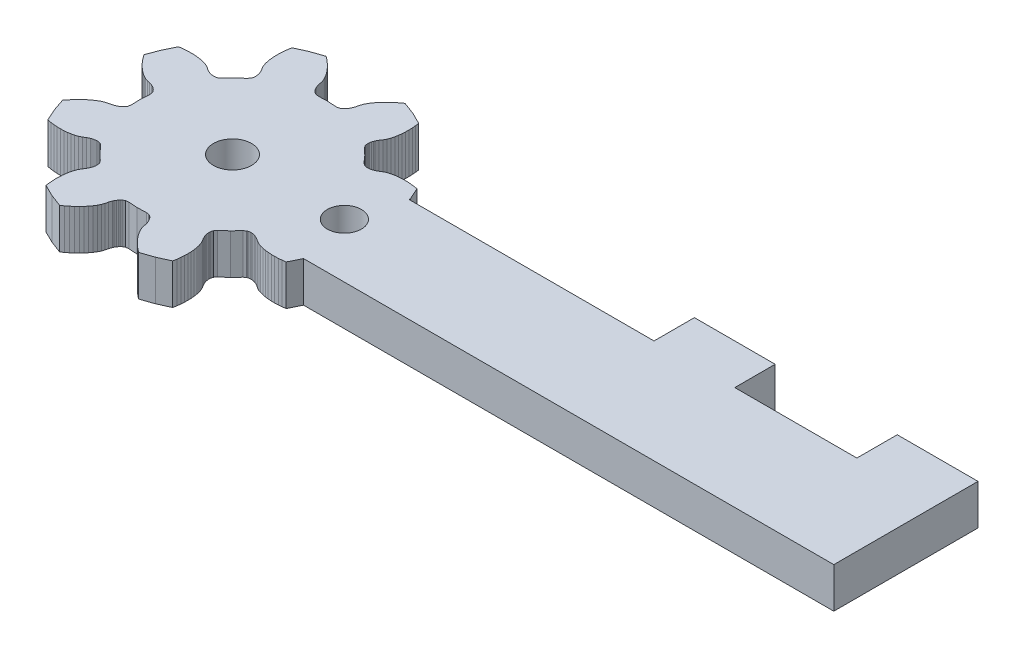
SolidWorks part; units mm, degrees
ref_plane "Front Plane" through (0, 0, 0) normal (0, 0, 1) x (1, 0, 0)
ref_plane "Top Plane" through (0, 0, 0) normal (0, 1, 0) x (1, 0, 0)
ref_plane "Right Plane" through (0, 0, 0) normal (1, 0, 0) x (0, 0, -1)
sketch "Sketch1" plane through (0, 0, 0) normal (0, 1, 0) x (1, 0, 0)
  line L0 (118.5341, 166.0961) -> (137.7907, 166.0961)
  line L1 (160.0907, 166.0961) -> (160.0907, 157.9324)
  line L2 (160.0907, 157.9324) -> (118.4045, 157.9258)
  line L3 (160.0907, 166.0961) -> (160.0907, 169.2711)
  line L4 (160.0907, 169.2711) -> (153.7407, 169.2711)
  line L5 (153.7407, 169.2711) -> (153.7407, 166.0961)
  line L7 (144.1407, 166.0961) -> (144.1407, 169.2711)
  line L8 (144.1407, 169.2711) -> (137.7907, 169.2711)
  line L9 (137.7907, 169.2711) -> (137.7907, 166.0961)
  line L10 (144.1407, 166.0961) -> (153.7407, 166.0961)
  line L1608 (118.5341, 166.0961) -> (118.5341, 166.193)
  line L1609 (118.5341, 166.193) -> (118.1081, 167.1345)
  line L1610 (118.1081, 167.1345) -> (117.8266, 167.1811)
  line L1611 (117.8266, 167.1811) -> (117.5494, 167.2141)
  line L1612 (117.5494, 167.2141) -> (117.277, 167.2336)
  line L1613 (117.277, 167.2336) -> (117.0101, 167.2392)
  line L1614 (117.0101, 167.2392) -> (116.7493, 167.2309)
  line L1615 (116.7493, 167.2309) -> (116.4956, 167.2082)
  line L1616 (116.4956, 167.2082) -> (116.2497, 167.1704)
  line L1617 (116.2497, 167.1704) -> (116.0133, 167.1164)
  line L1618 (116.0133, 167.1164) -> (115.7883, 167.0435)
  line L1619 (115.7883, 167.0435) -> (115.5824, 166.9415)
  line L1620 (115.5824, 166.9415) -> (115.3904, 166.8184)
  line L1621 (115.3904, 166.8184) -> (115.1836, 166.7174)
  line L1622 (115.1836, 166.7174) -> (115.0732, 166.6772)
  line L1623 (115.0732, 166.6772) -> (114.9567, 166.6456)
  line L1624 (114.9567, 166.6456) -> (114.8323, 166.6253)
  line L1625 (114.8323, 166.6253) -> (114.766, 166.6206)
  line L1626 (114.766, 166.6206) -> (114.696, 166.6208)
  line L1627 (114.696, 166.6208) -> (114.6211, 166.6276)
  line L1628 (114.6211, 166.6276) -> (114.5385, 166.6443)
  line L1629 (114.5385, 166.6443) -> (114.4416, 166.6792)
  line L1630 (114.4416, 166.6792) -> (114.2616, 166.8186)
  line L1631 (114.2616, 166.8186) -> (113.7953, 167.3484)
  line L1632 (113.7953, 167.3484) -> (113.2804, 167.8311)
  line L1633 (113.2804, 167.8311) -> (113.1468, 168.0154)
  line L1634 (113.1468, 168.0154) -> (113.1149, 168.1133)
  line L1635 (113.1149, 168.1133) -> (113.1008, 168.1964)
  line L1636 (113.1008, 168.1964) -> (113.0963, 168.2716)
  line L1637 (113.0963, 168.2716) -> (113.0983, 168.3415)
  line L1638 (113.0983, 168.3415) -> (113.1051, 168.4076)
  line L1639 (113.1051, 168.4076) -> (113.1293, 168.5313)
  line L1640 (113.1293, 168.5313) -> (113.1645, 168.6468)
  line L1641 (113.1645, 168.6468) -> (113.2082, 168.7559)
  line L1642 (113.2082, 168.7559) -> (113.3157, 168.9594)
  line L1643 (113.3157, 168.9594) -> (113.4447, 169.1474)
  line L1644 (113.4447, 169.1474) -> (113.5532, 169.35)
  line L1645 (113.5532, 169.35) -> (113.633, 169.5726)
  line L1646 (113.633, 169.5726) -> (113.6945, 169.8072)
  line L1647 (113.6945, 169.8072) -> (113.74, 170.0517)
  line L1648 (113.74, 170.0517) -> (113.7706, 170.3047)
  line L1649 (113.7706, 170.3047) -> (113.7871, 170.565)
  line L1650 (113.7871, 170.565) -> (113.7899, 170.832)
  line L1651 (113.7899, 170.832) -> (113.779, 171.1049)
  line L1652 (113.779, 171.1049) -> (113.7547, 171.383)
  line L1653 (113.7547, 171.383) -> (113.717, 171.6658)
  line L1654 (113.717, 171.6658) -> (112.7893, 172.1212)
  line L1655 (112.7893, 172.1212) -> (111.8223, 172.4857)
  line L1656 (111.8223, 172.4857) -> (111.5903, 172.3196)
  line L1657 (111.5903, 172.3196) -> (111.371, 172.1469)
  line L1658 (111.371, 172.1469) -> (111.1646, 171.9681)
  line L1659 (111.1646, 171.9681) -> (110.9718, 171.7833)
  line L1660 (110.9718, 171.7833) -> (110.7934, 171.593)
  line L1661 (110.7934, 171.593) -> (110.63, 171.3975)
  line L1662 (110.63, 171.3975) -> (110.4829, 171.197)
  line L1663 (110.4829, 171.197) -> (110.3539, 170.9916)
  line L1664 (110.3539, 170.9916) -> (110.2464, 170.781)
  line L1665 (110.2464, 170.781) -> (110.1728, 170.5633)
  line L1666 (110.1728, 170.5633) -> (110.1241, 170.3405)
  line L1667 (110.1241, 170.3405) -> (110.0493, 170.1228)
  line L1668 (110.0493, 170.1228) -> (109.9997, 170.0163)
  line L1669 (109.9997, 170.0163) -> (109.9397, 169.9116)
  line L1670 (109.9397, 169.9116) -> (109.8661, 169.8092)
  line L1671 (109.8661, 169.8092) -> (109.8225, 169.759)
  line L1672 (109.8225, 169.759) -> (109.7729, 169.7097)
  line L1673 (109.7729, 169.7097) -> (109.715, 169.6615)
  line L1674 (109.715, 169.6615) -> (109.6448, 169.615)
  line L1675 (109.6448, 169.615) -> (109.5516, 169.5712)
  line L1676 (109.5516, 169.5712) -> (109.3258, 169.5424)
  line L1677 (109.3258, 169.5424) -> (108.6215, 169.5873)
  line L1678 (108.6215, 169.5873) -> (107.9161, 169.5646)
  line L1679 (107.9161, 169.5646) -> (107.6912, 169.6004)
  line L1680 (107.6912, 169.6004) -> (107.5995, 169.6471)
  line L1681 (107.5995, 169.6471) -> (107.5307, 169.6959)
  line L1682 (107.5307, 169.6959) -> (107.4745, 169.7459)
  line L1683 (107.4745, 169.7459) -> (107.4264, 169.7967)
  line L1684 (107.4264, 169.7967) -> (107.3844, 169.8482)
  line L1685 (107.3844, 169.8482) -> (107.3141, 169.9529)
  line L1686 (107.3141, 169.9529) -> (107.2574, 170.0594)
  line L1687 (107.2574, 170.0594) -> (107.2111, 170.1674)
  line L1688 (107.2111, 170.1674) -> (107.1432, 170.3873)
  line L1689 (107.1432, 170.3873) -> (107.1015, 170.6115)
  line L1690 (107.1015, 170.6115) -> (107.0349, 170.8315)
  line L1691 (107.0349, 170.8315) -> (106.934, 171.0453)
  line L1692 (106.934, 171.0453) -> (106.8116, 171.2547)
  line L1693 (106.8116, 171.2547) -> (106.6708, 171.4597)
  line L1694 (106.6708, 171.4597) -> (106.5136, 171.6603)
  line L1695 (106.5136, 171.6603) -> (106.3412, 171.856)
  line L1696 (106.3412, 171.856) -> (106.1543, 172.0467)
  line L1697 (106.1543, 172.0467) -> (105.9537, 172.232)
  line L1698 (105.9537, 172.232) -> (105.7399, 172.4115)
  line L1699 (105.7399, 172.4115) -> (105.5133, 172.5848)
  line L1700 (105.5133, 172.5848) -> (104.5353, 172.2508)
  line L1701 (104.5353, 172.2508) -> (103.5937, 171.8248)
  line L1702 (103.5937, 171.8248) -> (103.5472, 171.5433)
  line L1703 (103.5472, 171.5433) -> (103.5141, 171.2661)
  line L1704 (103.5141, 171.2661) -> (103.4947, 170.9937)
  line L1705 (103.4947, 170.9937) -> (103.489, 170.7268)
  line L1706 (103.489, 170.7268) -> (103.4974, 170.4661)
  line L1707 (103.4974, 170.4661) -> (103.52, 170.2122)
  line L1708 (103.52, 170.2122) -> (103.5578, 169.9665)
  line L1709 (103.5578, 169.9665) -> (103.6119, 169.73)
  line L1710 (103.6119, 169.73) -> (103.6847, 169.5051)
  line L1711 (103.6847, 169.5051) -> (103.7867, 169.2991)
  line L1712 (103.7867, 169.2991) -> (103.9099, 169.1071)
  line L1713 (103.9099, 169.1071) -> (104.0108, 168.9003)
  line L1714 (104.0108, 168.9003) -> (104.0511, 168.7899)
  line L1715 (104.0511, 168.7899) -> (104.0826, 168.6735)
  line L1716 (104.0826, 168.6735) -> (104.103, 168.549)
  line L1717 (104.103, 168.549) -> (104.1077, 168.4827)
  line L1718 (104.1077, 168.4827) -> (104.1075, 168.4127)
  line L1719 (104.1075, 168.4127) -> (104.1006, 168.3378)
  line L1720 (104.1006, 168.3378) -> (104.0839, 168.2552)
  line L1721 (104.0839, 168.2552) -> (104.049, 168.1583)
  line L1722 (104.049, 168.1583) -> (103.9096, 167.9783)
  line L1723 (103.9096, 167.9783) -> (103.3799, 167.512)
  line L1724 (103.3799, 167.512) -> (102.8972, 166.9971)
  line L1725 (102.8972, 166.9971) -> (102.7129, 166.8635)
  line L1726 (102.7129, 166.8635) -> (102.6149, 166.8316)
  line L1727 (102.6149, 166.8316) -> (102.5318, 166.8175)
  line L1728 (102.5318, 166.8175) -> (102.4567, 166.8131)
  line L1729 (102.4567, 166.8131) -> (102.3868, 166.815)
  line L1730 (102.3868, 166.815) -> (102.3207, 166.8218)
  line L1731 (102.3207, 166.8218) -> (102.1969, 166.8461)
  line L1732 (102.1969, 166.8461) -> (102.0815, 166.8813)
  line L1733 (102.0815, 166.8813) -> (101.9724, 166.9249)
  line L1734 (101.9724, 166.9249) -> (101.7689, 167.0324)
  line L1735 (101.7689, 167.0324) -> (101.5809, 167.1615)
  line L1736 (101.5809, 167.1615) -> (101.3782, 167.2699)
  line L1737 (101.3782, 167.2699) -> (101.1557, 167.3498)
  line L1738 (101.1557, 167.3498) -> (100.921, 167.4112)
  line L1739 (100.921, 167.4112) -> (100.6765, 167.4567)
  line L1740 (100.6765, 167.4567) -> (100.4236, 167.4874)
  line L1741 (100.4236, 167.4874) -> (100.1632, 167.5039)
  line L1742 (100.1632, 167.5039) -> (99.8963, 167.5066)
  line L1743 (99.8963, 167.5066) -> (99.6234, 167.4957)
  line L1744 (99.6234, 167.4957) -> (99.3453, 167.4714)
  line L1745 (99.3453, 167.4714) -> (99.0625, 167.4337)
  line L1746 (99.0625, 167.4337) -> (98.6071, 166.506)
  line L1747 (98.6071, 166.506) -> (98.2426, 165.539)
  line L1748 (98.2426, 165.539) -> (98.4087, 165.3071)
  line L1749 (98.4087, 165.3071) -> (98.5813, 165.0877)
  line L1750 (98.5813, 165.0877) -> (98.7602, 164.8813)
  line L1751 (98.7602, 164.8813) -> (98.9449, 164.6886)
  line L1752 (98.9449, 164.6886) -> (99.1352, 164.5101)
  line L1753 (99.1352, 164.5101) -> (99.3307, 164.3467)
  line L1754 (99.3307, 164.3467) -> (99.5312, 164.1996)
  line L1755 (99.5312, 164.1996) -> (99.7367, 164.0706)
  line L1756 (99.7367, 164.0706) -> (99.9472, 163.9631)
  line L1757 (99.9472, 163.9631) -> (100.165, 163.8895)
  line L1758 (100.165, 163.8895) -> (100.3878, 163.8409)
  line L1759 (100.3878, 163.8409) -> (100.6054, 163.7661)
  line L1760 (100.6054, 163.7661) -> (100.7119, 163.7165)
  line L1761 (100.7119, 163.7165) -> (100.8166, 163.6564)
  line L1762 (100.8166, 163.6564) -> (100.919, 163.5828)
  line L1763 (100.919, 163.5828) -> (100.9692, 163.5392)
  line L1764 (100.9692, 163.5392) -> (101.0185, 163.4896)
  line L1765 (101.0185, 163.4896) -> (101.0667, 163.4318)
  line L1766 (101.0667, 163.4318) -> (101.1133, 163.3615)
  line L1767 (101.1133, 163.3615) -> (101.1571, 163.2683)
  line L1768 (101.1571, 163.2683) -> (101.1858, 163.0425)
  line L1769 (101.1858, 163.0425) -> (101.1409, 162.3382)
  line L1770 (101.1409, 162.3382) -> (101.1637, 161.6328)
  line L1771 (101.1637, 161.6328) -> (101.1279, 161.408)
  line L1772 (101.1279, 161.408) -> (101.0812, 161.3162)
  line L1773 (101.0812, 161.3162) -> (101.0324, 161.2475)
  line L1774 (101.0324, 161.2475) -> (100.9824, 161.1912)
  line L1775 (100.9824, 161.1912) -> (100.9316, 161.1431)
  line L1776 (100.9316, 161.1431) -> (100.88, 161.1012)
  line L1777 (100.88, 161.1012) -> (100.7753, 161.0308)
  line L1778 (100.7753, 161.0308) -> (100.6689, 160.9741)
  line L1779 (100.6689, 160.9741) -> (100.5608, 160.9278)
  line L1780 (100.5608, 160.9278) -> (100.341, 160.8599)
  line L1781 (100.341, 160.8599) -> (100.1167, 160.8183)
  line L1782 (100.1167, 160.8183) -> (99.8968, 160.7516)
  line L1783 (99.8968, 160.7516) -> (99.6829, 160.6507)
  line L1784 (99.6829, 160.6507) -> (99.4736, 160.5283)
  line L1785 (99.4736, 160.5283) -> (99.2685, 160.3876)
  line L1786 (99.2685, 160.3876) -> (99.068, 160.2304)
  line L1787 (99.068, 160.2304) -> (98.8722, 160.0579)
  line L1788 (98.8722, 160.0579) -> (98.6815, 159.8711)
  line L1789 (98.6815, 159.8711) -> (98.4962, 159.6704)
  line L1790 (98.4962, 159.6704) -> (98.3167, 159.4566)
  line L1791 (98.3167, 159.4566) -> (98.1435, 159.23)
  line L1792 (98.1435, 159.23) -> (98.4774, 158.252)
  line L1793 (98.4774, 158.252) -> (98.9034, 157.3104)
  line L1794 (98.9034, 157.3104) -> (99.1849, 157.2639)
  line L1795 (99.1849, 157.2639) -> (99.4621, 157.2308)
  line L1796 (99.4621, 157.2308) -> (99.7345, 157.2114)
  line L1797 (99.7345, 157.2114) -> (100.0015, 157.2058)
  line L1798 (100.0015, 157.2058) -> (100.2622, 157.2141)
  line L1799 (100.2622, 157.2141) -> (100.516, 157.2368)
  line L1800 (100.516, 157.2368) -> (100.7618, 157.2745)
  line L1801 (100.7618, 157.2745) -> (100.9983, 157.3286)
  line L1802 (100.9983, 157.3286) -> (101.2232, 157.4015)
  line L1803 (101.2232, 157.4015) -> (101.4292, 157.5035)
  line L1804 (101.4292, 157.5035) -> (101.6211, 157.6266)
  line L1805 (101.6211, 157.6266) -> (101.8279, 157.7276)
  line L1806 (101.8279, 157.7276) -> (101.9383, 157.7678)
  line L1807 (101.9383, 157.7678) -> (102.0548, 157.7994)
  line L1808 (102.0548, 157.7994) -> (102.1793, 157.8197)
  line L1809 (102.1793, 157.8197) -> (102.2455, 157.8244)
  line L1810 (102.2455, 157.8244) -> (102.3155, 157.8242)
  line L1811 (102.3155, 157.8242) -> (102.3905, 157.8174)
  line L1812 (102.3905, 157.8174) -> (102.4731, 157.8007)
  line L1813 (102.4731, 157.8007) -> (102.5699, 157.7657)
  line L1814 (102.5699, 157.7657) -> (102.7499, 157.6264)
  line L1815 (102.7499, 157.6264) -> (103.2163, 157.0966)
  line L1816 (103.2163, 157.0966) -> (103.7311, 156.6139)
  line L1817 (103.7311, 156.6139) -> (103.8648, 156.4296)
  line L1818 (103.8648, 156.4296) -> (103.8966, 156.3317)
  line L1819 (103.8966, 156.3317) -> (103.9107, 156.2486)
  line L1820 (103.9107, 156.2486) -> (103.9152, 156.1734)
  line L1821 (103.9152, 156.1734) -> (103.9132, 156.1035)
  line L1822 (103.9132, 156.1035) -> (103.9065, 156.0374)
  line L1823 (103.9065, 156.0374) -> (103.8822, 155.9136)
  line L1824 (103.8822, 155.9136) -> (103.847, 155.7982)
  line L1825 (103.847, 155.7982) -> (103.8033, 155.6891)
  line L1826 (103.8033, 155.6891) -> (103.6959, 155.4856)
  line L1827 (103.6959, 155.4856) -> (103.5668, 155.2976)
  line L1828 (103.5668, 155.2976) -> (103.4584, 155.0949)
  line L1829 (103.4584, 155.0949) -> (103.3785, 154.8724)
  line L1830 (103.3785, 154.8724) -> (103.317, 154.6378)
  line L1831 (103.317, 154.6378) -> (103.2715, 154.3933)
  line L1832 (103.2715, 154.3933) -> (103.2409, 154.1403)
  line L1833 (103.2409, 154.1403) -> (103.2244, 153.8799)
  line L1834 (103.2244, 153.8799) -> (103.2217, 153.613)
  line L1835 (103.2217, 153.613) -> (103.2325, 153.3401)
  line L1836 (103.2325, 153.3401) -> (103.2568, 153.062)
  line L1837 (103.2568, 153.062) -> (103.2945, 152.7792)
  line L1838 (103.2945, 152.7792) -> (104.2222, 152.3238)
  line L1839 (104.2222, 152.3238) -> (105.1892, 151.9593)
  line L1840 (105.1892, 151.9593) -> (105.4212, 152.1254)
  line L1841 (105.4212, 152.1254) -> (105.6406, 152.298)
  line L1842 (105.6406, 152.298) -> (105.8469, 152.4769)
  line L1843 (105.8469, 152.4769) -> (106.0397, 152.6617)
  line L1844 (106.0397, 152.6617) -> (106.2182, 152.8519)
  line L1845 (106.2182, 152.8519) -> (106.3816, 153.0474)
  line L1846 (106.3816, 153.0474) -> (106.5287, 153.248)
  line L1847 (106.5287, 153.248) -> (106.6576, 153.4534)
  line L1848 (106.6576, 153.4534) -> (106.7652, 153.6639)
  line L1849 (106.7652, 153.6639) -> (106.8387, 153.8817)
  line L1850 (106.8387, 153.8817) -> (106.8874, 154.1045)
  line L1851 (106.8874, 154.1045) -> (106.9622, 154.3221)
  line L1852 (106.9622, 154.3221) -> (107.0118, 154.4286)
  line L1853 (107.0118, 154.4286) -> (107.0719, 154.5333)
  line L1854 (107.0719, 154.5333) -> (107.1455, 154.6358)
  line L1855 (107.1455, 154.6358) -> (107.189, 154.6859)
  line L1856 (107.189, 154.6859) -> (107.2386, 154.7352)
  line L1857 (107.2386, 154.7352) -> (107.2965, 154.7834)
  line L1858 (107.2965, 154.7834) -> (107.3667, 154.83)
  line L1859 (107.3667, 154.83) -> (107.4599, 154.8738)
  line L1860 (107.4599, 154.8738) -> (107.6857, 154.9026)
  line L1861 (107.6857, 154.9026) -> (108.3901, 154.8577)
  line L1862 (108.3901, 154.8577) -> (109.0955, 154.8804)
  line L1863 (109.0955, 154.8804) -> (109.3203, 154.8446)
  line L1864 (109.3203, 154.8446) -> (109.4121, 154.7979)
  line L1865 (109.4121, 154.7979) -> (109.4808, 154.7491)
  line L1866 (109.4808, 154.7491) -> (109.5371, 154.6991)
  line L1867 (109.5371, 154.6991) -> (109.5851, 154.6483)
  line L1868 (109.5851, 154.6483) -> (109.6271, 154.5968)
  line L1869 (109.6271, 154.5968) -> (109.6974, 154.4921)
  line L1870 (109.6974, 154.4921) -> (109.7542, 154.3856)
  line L1871 (109.7542, 154.3856) -> (109.8004, 154.2775)
  line L1872 (109.8004, 154.2775) -> (109.8684, 154.0577)
  line L1873 (109.8684, 154.0577) -> (109.91, 153.8335)
  line L1874 (109.91, 153.8335) -> (109.9767, 153.6135)
  line L1875 (109.9767, 153.6135) -> (110.0775, 153.3997)
  line L1876 (110.0775, 153.3997) -> (110.2, 153.1903)
  line L1877 (110.2, 153.1903) -> (110.3407, 152.9852)
  line L1878 (110.3407, 152.9852) -> (110.4979, 152.7847)
  line L1879 (110.4979, 152.7847) -> (110.6703, 152.5889)
  line L1880 (110.6703, 152.5889) -> (110.8572, 152.3982)
  line L1881 (110.8572, 152.3982) -> (111.0578, 152.213)
  line L1882 (111.0578, 152.213) -> (111.2717, 152.0335)
  line L1883 (111.2717, 152.0335) -> (111.4983, 151.8602)
  line L1884 (111.4983, 151.8602) -> (112.4763, 152.1941)
  line L1885 (112.4763, 152.1941) -> (113.4178, 152.6202)
  line L1886 (113.4178, 152.6202) -> (113.4644, 152.9016)
  line L1887 (113.4644, 152.9016) -> (113.4974, 153.1789)
  line L1888 (113.4974, 153.1789) -> (113.5168, 153.4513)
  line L1889 (113.5168, 153.4513) -> (113.5225, 153.7182)
  line L1890 (113.5225, 153.7182) -> (113.5142, 153.9789)
  line L1891 (113.5142, 153.9789) -> (113.4915, 154.2327)
  line L1892 (113.4915, 154.2327) -> (113.4537, 154.4785)
  line L1893 (113.4537, 154.4785) -> (113.3996, 154.715)
  line L1894 (113.3996, 154.715) -> (113.3268, 154.9399)
  line L1895 (113.3268, 154.9399) -> (113.2248, 155.1459)
  line L1896 (113.2248, 155.1459) -> (113.1017, 155.3378)
  line L1897 (113.1017, 155.3378) -> (113.0007, 155.5446)
  line L1898 (113.0007, 155.5446) -> (112.9604, 155.655)
  line L1899 (112.9604, 155.655) -> (112.9289, 155.7715)
  line L1900 (112.9289, 155.7715) -> (112.9085, 155.896)
  line L1901 (112.9085, 155.896) -> (112.9038, 155.9623)
  line L1902 (112.9038, 155.9623) -> (112.9041, 156.0322)
  line L1903 (112.9041, 156.0322) -> (112.9109, 156.1072)
  line L1904 (112.9109, 156.1072) -> (112.9276, 156.1898)
  line L1905 (112.9276, 156.1898) -> (112.9625, 156.2866)
  line L1906 (112.9625, 156.2866) -> (113.1019, 156.4667)
  line L1907 (113.1019, 156.4667) -> (113.6316, 156.933)
  line L1908 (113.6316, 156.933) -> (114.1144, 157.4478)
  line L1909 (114.1144, 157.4478) -> (114.2987, 157.5815)
  line L1910 (114.2987, 157.5815) -> (114.3966, 157.6133)
  line L1911 (114.3966, 157.6133) -> (114.4797, 157.6275)
  line L1912 (114.4797, 157.6275) -> (114.5548, 157.6319)
  line L1913 (114.5548, 157.6319) -> (114.6247, 157.63)
  line L1914 (114.6247, 157.63) -> (114.6908, 157.6232)
  line L1915 (114.6908, 157.6232) -> (114.8146, 157.5989)
  line L1916 (114.8146, 157.5989) -> (114.9301, 157.5637)
  line L1917 (114.9301, 157.5637) -> (115.0392, 157.52)
  line L1918 (115.0392, 157.52) -> (115.2426, 157.4126)
  line L1919 (115.2426, 157.4126) -> (115.4307, 157.2835)
  line L1920 (115.4307, 157.2835) -> (115.6333, 157.1751)
  line L1921 (115.6333, 157.1751) -> (115.8558, 157.0952)
  line L1922 (115.8558, 157.0952) -> (116.0905, 157.0337)
  line L1923 (116.0905, 157.0337) -> (116.335, 156.9883)
  line L1924 (116.335, 156.9883) -> (116.5879, 156.9576)
  line L1925 (116.5879, 156.9576) -> (116.8483, 156.9411)
  line L1926 (116.8483, 156.9411) -> (117.1153, 156.9384)
  line L1927 (117.1153, 156.9384) -> (117.3881, 156.9492)
  line L1928 (117.3881, 156.9492) -> (117.6663, 156.9736)
  line L1929 (117.6663, 156.9736) -> (117.949, 157.0112)
  line L1930 (117.949, 157.0112) -> (118.4045, 157.9389)
  line L1931 (118.4045, 157.9389) -> (118.4045, 157.9258)
  circle A0 centre (108.5161, 162.2225) radius 1.5
  circle A1 centre (117.3319, 162.206) radius 1.3413
  dimension "D1" = 3.175
  dimension "D2" = 3.175
  dimension "D3" = 6.35
  dimension "D4" = 6.35
  dimension "D5" = 9.6
extrude "Boss-Extrude1" add sketch "Sketch1" along normal blind 3.175
